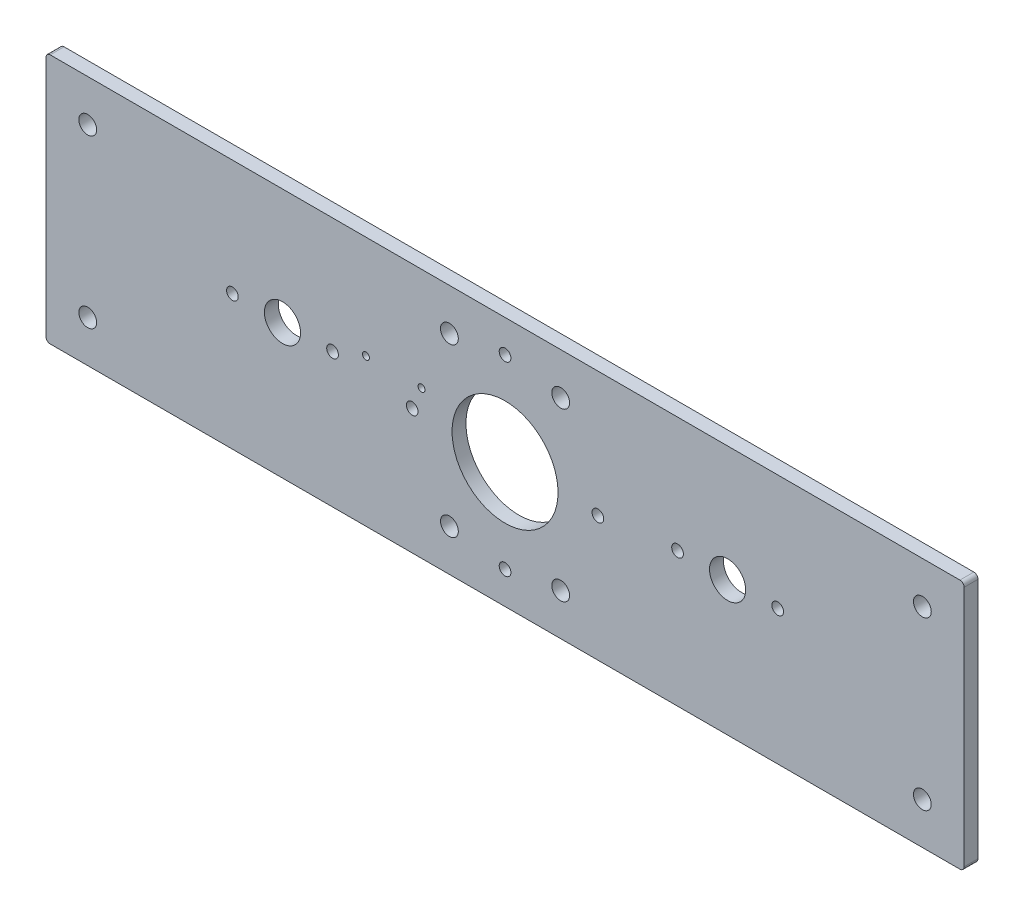
SolidWorks part; units mm, degrees
ref_plane "Front Plane" through (0, 0, 0) normal (0, 0, 1) x (1, 0, 0)
ref_plane "Top Plane" through (0, 0, 0) normal (0, 1, 0) x (1, 0, 0)
ref_plane "Right Plane" through (0, 0, 0) normal (1, 0, 0) x (0, 0, -1)
sketch "Sketch1" plane through (0, 0, 0) normal (0, 0, 1) x (1, 0, 0)
  line L1 (165, -45) -> (-165, -45)
  line L2 (165, -45) -> (165, 45)
  line L3 (165, 45) -> (-165, 45)
  line L4 (-165, -45) -> (-165, 45)
  line L5 (165, -45) -> (-165, 45) construction
  line L6 (165, 45) -> (-165, -45) construction
  circle A0 centre (0, 0) radius 19.05
  point P0 (0, 0)
  dimension "D3" = 38.1
  dimension "D1" = 90
  dimension "D2" = 330
extrude "Boss-Extrude1" add sketch "Sketch1" along normal mid plane 5
hole_wizard "M6 Clearance Hole1" positions "Sketch5" profile "Sketch4" hole size "M6" standard "ANSI Metric" end condition through all
sketch "Sketch5" plane through (0, 0, 2.5) normal (0, 0, 1) x (1, 0, 0)
  line L0 (165, 45) -> (-165, 45) construction
  line L1 (-165, 45) -> (-165, -45) construction
  line L2 (-165, -45) -> (165, -45) construction
  point P0 (-150, 30)
  point P2 (-20, 30)
  point P4 (-20, -30)
  point P6 (-150, -30)
  dimension "D1" = 15
  dimension "D2" = 20
  dimension "D3" = 15
  dimension "D4" = 15
  dimension "D5" = 15
  dimension "D6" = 15
  dimension "D7" = 15
  dimension "D8" = 20
sketch "Sketch4" plane through (-150, 30, 2.5) normal (1, 0, 0) x (0, -1, 0)
  line L0 (0, 0) -> (0, 5)
  line L1 (0, 5) -> (3.2, 5)
  line L2 (3.2, 5) -> (3.2, 0)
  line L5 (3.2, 0) -> (0, 0)
  line L11 (0, -6.35) -> (0, 107.95) construction
  dimension "Thru Hole Dia." = 6.4
  dimension "Thru Hole Depth" = 5
mirror "Mirror2" about plane through (0, 0, 0) normal (1, 0, 0) of "M6 Clearance Hole1"
sketch "Sketch3" plane through (0, 0, 2.5) normal (0, 0, 1) x (1, 0, 0)
  line L0 (0, 3.4) -> (-49.4534, 3.4) construction
  circle A2 centre (-80, 3.4) radius 6.5
  dimension "D3" = 13
  dimension "D4" = 80
  dimension "D7" = 3.4
extrude "Cut-Extrude2" cut sketch "Sketch3" against normal through all
hole_wizard "M5x0.8 Tapped Hole1" positions "Sketch7" profile "Sketch6" tap size "M5x0.8" standard "ANSI Metric" end condition through all
sketch "Sketch7" plane through (0, 0, 2.5) normal (0, 0, 1) x (1, 0, 0)
  line L0 (-1080, 3.4) -> (48920, 3.4) construction
  circle A0 centre (-80, 3.4) radius 6.5 construction
  point P0 (-98, 3.4)
  point P2 (-62, 3.4)
  dimension "D1" = 18
  dimension "D2" = 18
sketch "Sketch6" plane through (-98, 3.4, 2.5) normal (1, 0, 0) x (0, -1, 0)
  line L0 (0, 0) -> (0, 5)
  line L1 (0, 5) -> (2.1, 5)
  line L2 (2.1, 5) -> (2.1, 0)
  line L5 (2.1, 0) -> (0, 0)
  line L11 (0, -6.35) -> (0, 107.95) construction
  dimension "Thru Tap Drill Dia." = 4.2
  dimension "Thru Tap Drill Depth" = 5
cosmetic thread "Hole Thread1" parameters "D2"=5
cosmetic thread "Hole Thread2" parameters "D2"=5
mirror "Mirror1" about plane through (0, 0, 0) normal (1, 0, 0) of "M5x0.8 Tapped Hole1", "Cut-Extrude2"
hole_wizard "M5x0.8 Tapped Hole3" positions "Sketch9" profile "Sketch8" tap size "M5x0.8" standard "ANSI Metric" end condition through all
sketch "Sketch9" plane through (0, 0, 2.5) normal (0, 0, 1) x (1, 0, 0)
  line L1 (0, -33.3754) -> (33.3754, 0) construction
  line L2 (0, -33.3754) -> (-33.3754, 0) construction
  line L3 (-33.3754, 0) -> (0, 33.3754) construction
  line L4 (33.3754, 0) -> (0, 33.3754) construction
  line L5 (0, -33.3754) -> (0, 33.3754) construction
  line L6 (-33.3754, 0) -> (33.3754, 0) construction
  line L7 (-1000, 0) -> (49000, 0) construction
  point P1 (0, 33.3754)
  point P164 (0, -33.3754)
  point P165 (-33.3754, 0)
  point P166 (33.3754, 0)
  dimension "D1" = 47.2
  dimension "D2" = 47.2
  dimension "D3" = 90
  dimension "D4" = 90
  dimension "D5" = 90
  dimension "D6" = 90
  dimension "D7" = 23.6
  dimension "D8" = 23.6
sketch "Sketch8" plane through (0, 33.3754, 2.5) normal (1, 0, 0) x (0, -1, 0)
  line L0 (0, 0) -> (0, 5)
  line L1 (0, 5) -> (2.1, 5)
  line L2 (2.1, 5) -> (2.1, 0)
  line L5 (2.1, 0) -> (0, 0)
  line L11 (0, -6.35) -> (0, 107.95) construction
  dimension "Thru Tap Drill Dia." = 4.2
  dimension "Thru Tap Drill Depth" = 5
cosmetic thread "Hole Thread3" parameters "D2"=5
cosmetic thread "Hole Thread4" parameters "D2"=5
cosmetic thread "Hole Thread5" parameters "D2"=5
cosmetic thread "Hole Thread6" parameters "D2"=5
fillet "Fillet1" radius 1.5 4 edges at (-165, -45, 0) (165, -45, 0) (165, 45, 0) (-165, 45, 0)
hole_wizard "M3x0.5 Tapped Hole1" positions "Sketch12" profile "Sketch11" tap size "M3x0.5" standard "ANSI Metric" end condition through all
sketch "Sketch12" plane through (0, 0, 2.5) normal (0, 0, 1) x (1, 0, 0)
  line L0 (-50, 8) -> (-30, 8)
  point P0 (-50, 8)
  point P2 (-30, 8)
  dimension "D1" = 20
  dimension "D2" = 8
  dimension "D3" = 30
sketch "Sketch11" plane through (-50, 8, 2.5) normal (1, 0, 0) x (0, -1, 0)
  line L0 (0, 0) -> (0, 5)
  line L1 (0, 5) -> (1.25, 5)
  line L2 (1.25, 5) -> (1.25, 0)
  line L5 (1.25, 0) -> (0, 0)
  line L11 (0, -6.35) -> (0, 107.95) construction
  dimension "Thru Tap Drill Dia." = 2.5
  dimension "Thru Tap Drill Depth" = 5
cosmetic thread "Hole Thread7" parameters "D2"=3
cosmetic thread "Hole Thread8" parameters "D2"=3
equation "\"D4@Sketch3\"=160/2"
